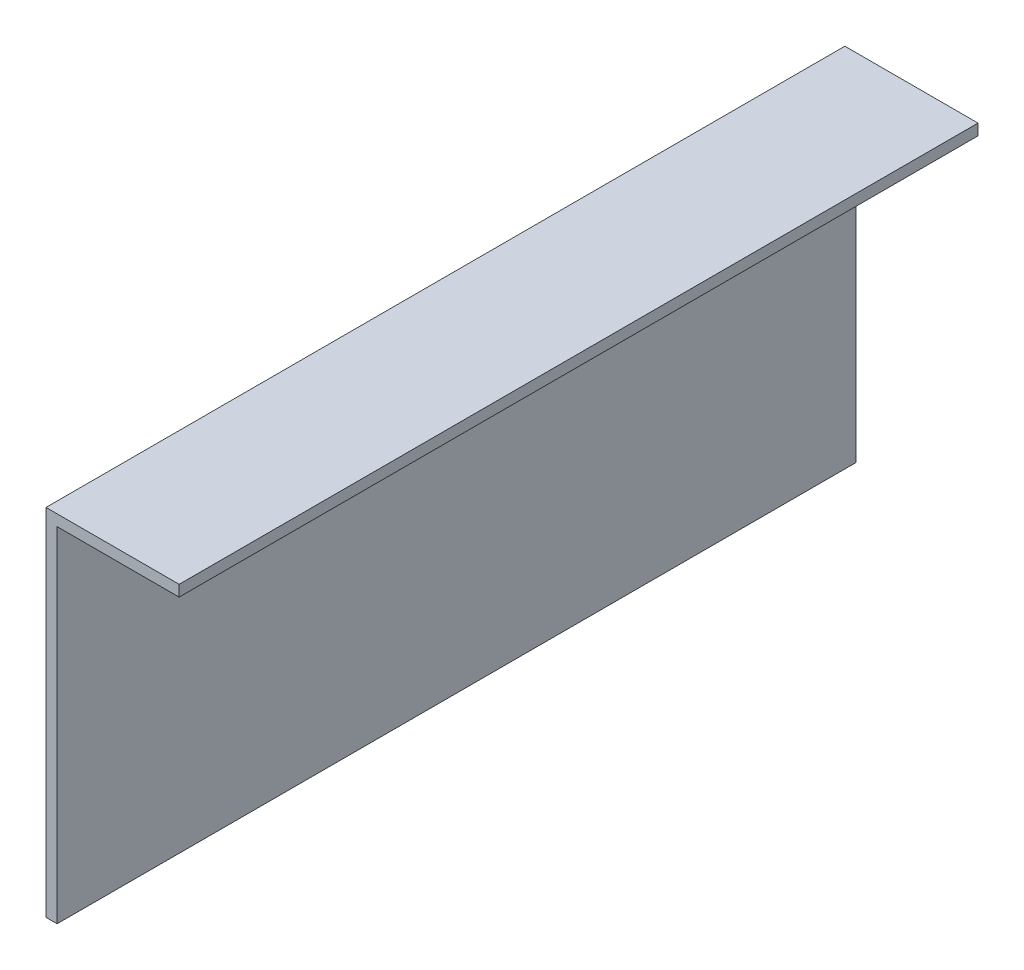
SolidWorks part; units mm, degrees
ref_plane "Front Plane" through (0, 0, 0) normal (0, 0, 1) x (1, 0, 0)
ref_plane "Top Plane" through (0, 0, 0) normal (0, 1, 0) x (1, 0, 0)
ref_plane "Right Plane" through (0, 0, 0) normal (1, 0, 0) x (0, 0, -1)
sketch "Sketch1" plane through (0, 0, 0) normal (0, 0, 1) x (1, 0, 0)
  line L0 (1.5875, 47.625) -> (36.5125, 47.625)
  line L1 (1.5875, -50.8) -> (-1.5875, -50.8)
  line L2 (1.5875, -50.8) -> (1.5875, 47.625)
  line L4 (-1.5875, -50.8) -> (-1.5875, 50.8)
  line L5 (1.5875, -50.8) -> (-1.5875, 50.8) construction
  line L6 (3.5127, 112.4075) -> (-1.5875, -50.8) construction
  line L7 (-1.5875, 50.8) -> (36.5125, 50.8)
  line L10 (36.5125, 50.8) -> (36.5125, 47.625)
  point P0 (0, 0)
  point P7 (0, -50.8)
  dimension "D1" = 3.175
  dimension "D2" = 3.175
  dimension "D3" = 38.1
  dimension "D4" = 101.6
extrude "Boss-Extrude1" add sketch "Sketch1" along normal blind 228.6
sketch "Sketch2" plane through (1.5875, 0, 0) normal (1, 0, 0) x (0, 0, -1)
  line L0 (-228.6, -29.4596) -> (0, 47.625) construction
  line L1 (-228.6, -50.8) -> (-228.6, 47.625) construction
  line L2 (-228.6, 47.625) -> (0, 47.625) construction
  line L3 (0, -50.8) -> (0, 47.625) construction
  point P6 (-32.8745, 47.625)
  point P7 (-4.2103, 47.625)
  point P8 (0, 47.625)
ref_plane "Plane1 - BACKBOARD PLANE" through (0, 42.7626, 14.4197) normal (0, -0.9476, -0.3195) x (0, 0.3195, -0.9476)
equation "\"eighthinch\"= 0.125"
equation "\"D2@Sketch1\"=\"eighthinch\""
